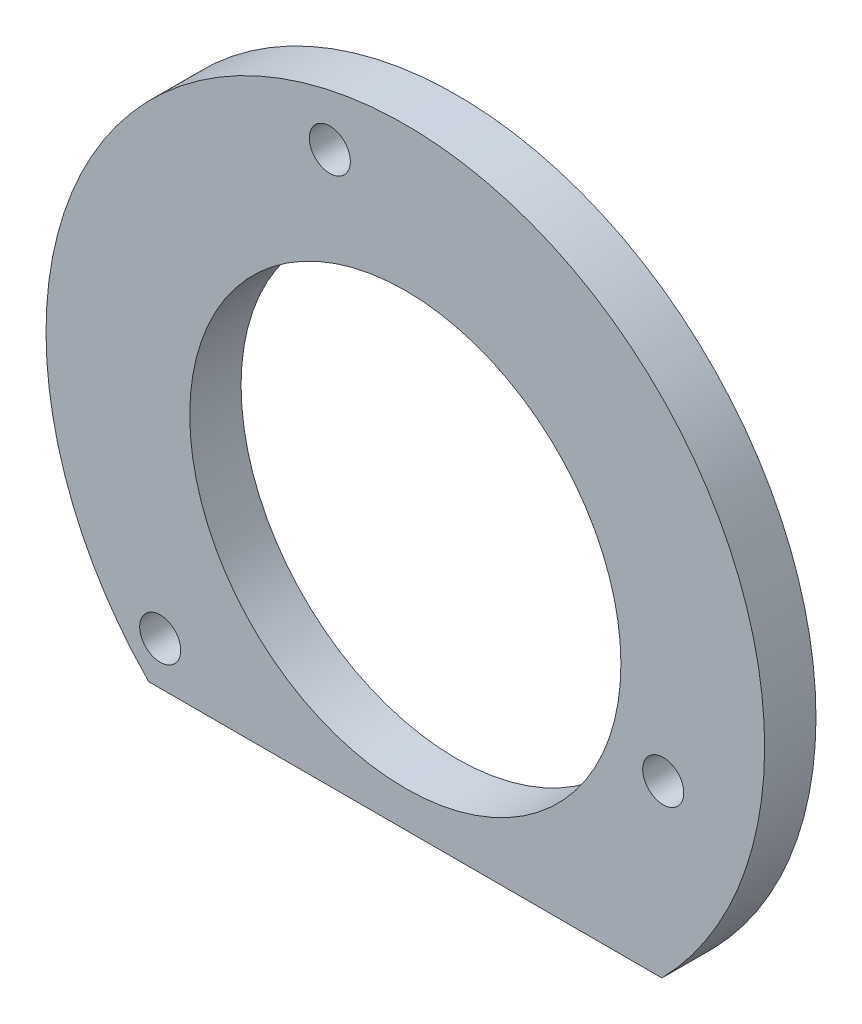
SolidWorks part; units mm, degrees
ref_plane "Front Plane" through (0, 0, 0) normal (0, 0, 1) x (1, 0, 0)
ref_plane "Top Plane" through (0, 0, 0) normal (0, 1, 0) x (1, 0, 0)
ref_plane "Right Plane" through (0, 0, 0) normal (1, 0, 0) x (0, 0, -1)
sketch "Sketch1" plane through (0, 0, 0) normal (0, 0, 1) x (1, 0, 0)
  circle A0 centre (0, 0) radius 35.56
  dimension "D1" = 71.12
extrude "Boss-Extrude1" add sketch "Sketch1" along normal blind 5.08
sketch "Sketch2" plane through (0, 0, 5.08) normal (0, 0, 1) x (1, 0, 0)
  line L0 (0, 0) -> (0, -35.56) construction
  line L6 (0, -35.56) -> (-36.2561, -35.56)
  line L7 (-36.2561, -35.56) -> (-36.2561, -24.892)
  line L8 (-36.2561, -24.892) -> (33.7504, -24.892)
  line L9 (33.7504, -24.892) -> (33.7504, -35.56)
  line L10 (33.7504, -35.56) -> (0, -35.56)
  circle A0 centre (0, 0) radius 35.56 construction
  dimension "D1" = 10.668
extrude "Cut-Extrude1" cut sketch "Sketch2" against normal through all
ref_axis "Axis1" through (0, -24.892, 0) along (0, 0, 1)
ref_plane "Plane1" through (0, 0, 0) normal (1, 0, 0) x (0, 0, 1)
sketch "Sketch7" plane through (0, 0, 5.08) normal (0, 0, 1) x (1, 0, 0)
  line L0 (-7.472, 29.6655) -> (-24.2611, -20.6265) construction
  line L1 (-7.472, 29.6655) -> (25.5229, -7.9528) construction
  line L2 (25.5229, -7.9528) -> (-24.2611, -20.6265) construction
  circle A0 centre (-24.2611, -20.6265) radius 2.032
  circle A1 centre (-7.472, 29.6655) radius 2.032
  circle A2 centre (25.5229, -7.9528) radius 2.032
  dimension "D1" = 4.064
  dimension "D2" = 50.292
  dimension "D3" = 50.038
  dimension "D4" = 49.784
extrude "Cut-Extrude2" cut sketch "Sketch7" against normal through all
sketch "Sketch8" plane through (0, 0, 0) normal (0, 0, -1) x (-1, 0, 0)
  circle A0 centre (0, 0) radius 21.336
  dimension "D1" = 42.672
extrude "Cut-Extrude3" cut sketch "Sketch8" against normal through all
equation "\"Foamcore\" = .1in"
equation "\"MDF\" = .2in"
equation "\"Gmaterial\"= \"MDF\""
equation "\"PVC-ID\" = \"1.590in\""
equation "\"PVC-OD\" = \"1.900in\""
equation "\"PVC-Sleeve-Width\" = \".51in\""
equation "\"D1@Boss-Extrude1\"=\"Gmaterial\""
